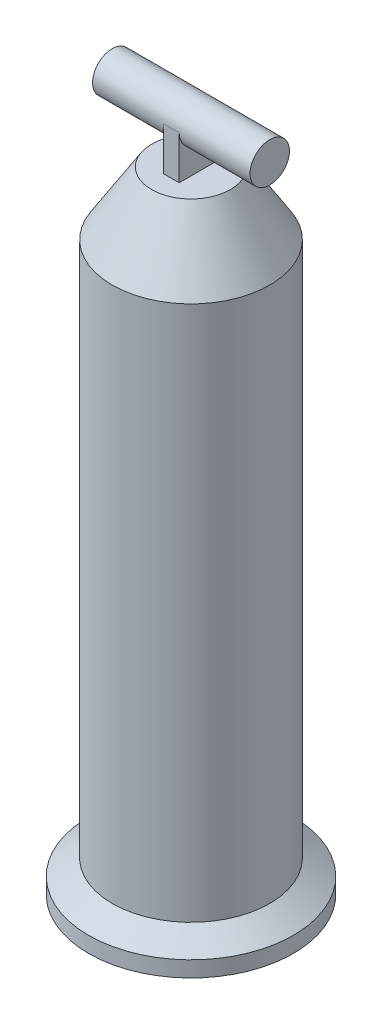
SolidWorks part; units mm, degrees
ref_plane "Front Plane" through (0, 0, 0) normal (0, 0, 1) x (1, 0, 0)
ref_plane "Top Plane" through (0, 0, 0) normal (0, 1, 0) x (1, 0, 0)
ref_plane "Right Plane" through (0, 0, 0) normal (1, 0, 0) x (0, 0, -1)
sketch "Sketch1" plane through (0, 0, 0) normal (1, 0, 0) x (0, 0, -1)
  line L0 (-10, 4) -> (-10, 72)
  line L1 (-10, 72) -> (-5, 80)
  line L2 (-5, 80) -> (0, 80)
  line L3 (0, 80) -> (0, 0) construction
  line L4 (-8, 71.4264) -> (0, 71.4264)
  line L5 (-8, 0) -> (-8, 71.4264)
  line L6 (0, 71.4264) -> (0, 80)
  line L7 (-10, 0) -> (-10, 72) construction
  line L8 (-10, 4) -> (-13, 2)
  line L9 (-3.8915, 78) -> (0, 78) construction
  line L10 (-8, 71.4264) -> (-3.8915, 78) construction
  line L11 (-13, 2) -> (-13, 0)
  line L12 (-13, 0) -> (-8, 0)
  dimension "D1" = 2
  dimension "D2" = 10
  dimension "D3" = 80
  dimension "D4" = 8
  dimension "D5" = 5
  dimension "D6" = 5
  dimension "D7" = 2
  dimension "D8" = 4
revolve "Revolve1" add sketch "Sketch1" angle 360 about L3
sketch "Sketch2" plane through (0, 80, 0) normal (0, 1, 0) x (1, 0, 0)
  line L0 (0, 2.5) -> (0, -2.5) construction
  line L1 (-1, 2.5) -> (1, 2.5)
  line L2 (1, 2.5) -> (1, -2.5)
  line L3 (1, -2.5) -> (-1, -2.5)
  line L4 (-1, -2.5) -> (-1, 2.5)
  dimension "D1" = 2
  dimension "D2" = 5
extrude "Boss-Extrude1" add sketch "Sketch2" along normal blind 8
sketch "Sketch3" plane through (-1, 0, 0) normal (-1, 0, 0) x (0, 0, 1)
  line L0 (-2.5, 88) -> (2.5, 88) construction
  line L1 (2.5, 88) -> (2.5, 80) construction
  line L2 (-2.5, 85.5) -> (-2.5, 90.5)
  line L3 (-2.5, 90.5) -> (2.5, 90.5)
  line L4 (2.5, 90.5) -> (2.5, 85.5)
  circle A0 centre (0, 85.5) radius 2.5
  line M2 (2.5, 80) -> (2.5, 88)
  line M3 (2.5, 88) -> (-2.5, 88)
  line M4 (-2.5, 88) -> (-2.5, 80)
  dimension "D1" = 5
  dimension "D2" = 5
extrude "Cut-Extrude1" cut sketch "Sketch3" against normal through all and the other way through all contours A0 M2 M3 | A0 M3 M4 | L4 L3 L2 M3 region at (-1, 87.4416, -1.9416) region at (-1, 89.25, 0) region at (-1, 87.4416, 1.9416)
extrude "Boss-Extrude2" add sketch "Sketch3<3>" along normal blind 9 and the other way blind 11 contours A0 region at (-1, 85.5, 0)
sketch "Sketch3<3>" plane through (-1, 0, 0) normal (-1, 0, 0) x (0, 0, 1) same geometry as "Sketch3"
